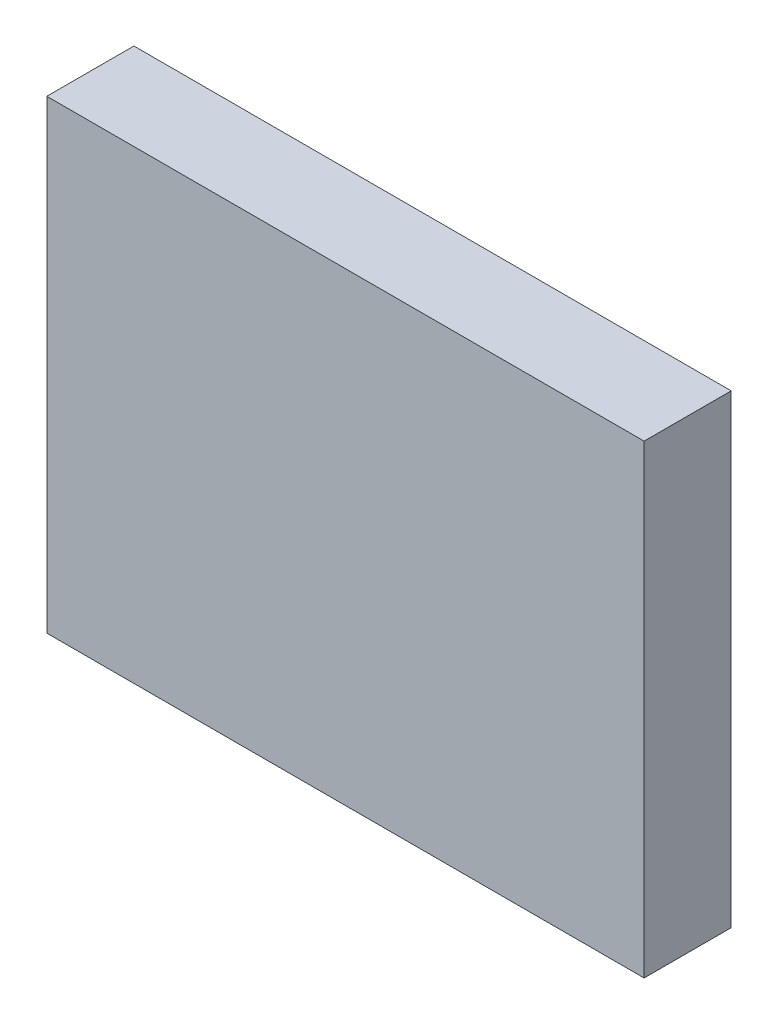
SolidWorks part; units mm, degrees
ref_plane "Front" through (0, 0, 0) normal (0, 0, 1) x (1, 0, 0)
ref_plane "Top" through (0, 0, 0) normal (0, 1, 0) x (1, 0, 0)
ref_plane "Right" through (0, 0, 0) normal (1, 0, 0) x (0, 0, -1)
sketch "Sketch1" plane through (0, 0, 0) normal (0, 0, 1) x (1, 0, 0)
  line L1 (-34.3, 26.7) -> (34.3, 26.7)
  line L2 (-34.3, 26.7) -> (-34.3, -26.7)
  line L3 (-34.3, -26.7) -> (34.3, -26.7)
  line L4 (34.3, 26.7) -> (34.3, -26.7)
  line L5 (-34.3, 26.7) -> (34.3, -26.7) construction
  line L6 (-34.3, -26.7) -> (34.3, 26.7) construction
  point P0 (0, 0)
  dimension "D1" = 68.6
  dimension "D2" = 53.4
extrude "Boss-Extrude1" add sketch "Sketch1" along normal blind 10
